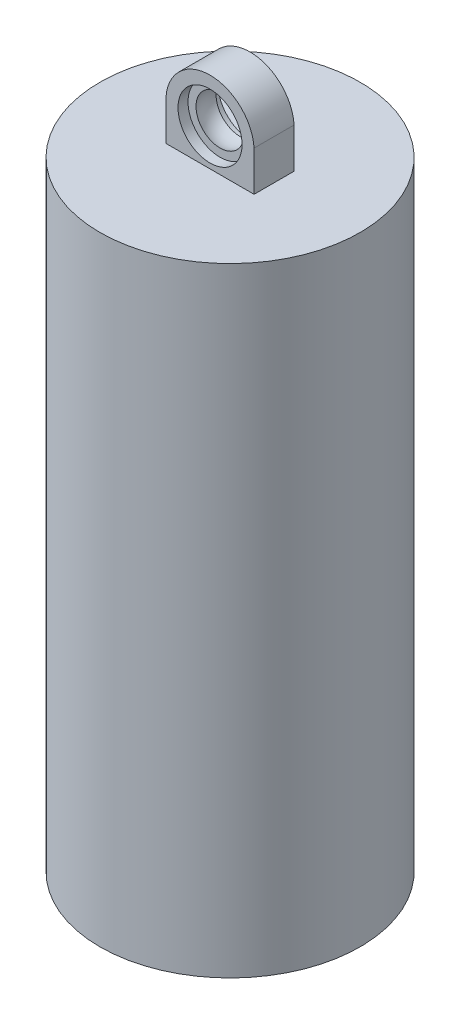
SolidWorks part; units mm, degrees
ref_plane "前视基准面" through (0, 0, 0) normal (0, 0, 1) x (1, 0, 0)
ref_plane "上视基准面" through (0, 0, 0) normal (0, 1, 0) x (1, 0, 0)
ref_plane "右视基准面" through (0, 0, 0) normal (1, 0, 0) x (0, 0, -1)
sketch "草图1" plane through (0, 0, 0) normal (0, 1, 0) x (1, 0, 0)
  circle A0 centre (0, 0) radius 32.5
  dimension "D1" = 65
extrude "凸台-拉伸1" add sketch "草图1" along normal blind 154.5
sketch "草图2" plane through (0, 0, 0) normal (0, -1, 0) x (1, 0, 0)
  circle A0 centre (0, 0) radius 12.5
  dimension "D1" = 25
extrude "凸台-拉伸2" add sketch "草图2" along normal blind 6
sketch "草图3" plane through (0, -6, 0) normal (0, -1, 0) x (1, 0, 0)
  circle A0 centre (0, 0) radius 6
  dimension "D1" = 12
extrude "切除-拉伸1" cut sketch "草图3" against normal blind 80
sketch "草图4" plane through (0, 0, 0) normal (0, 0, 1) x (1, 0, 0)
  line L0 (32.5, 154.5) -> (-32.5, 154.5) construction
  line L1 (-11, 154.5) -> (11, 154.5)
  line L2 (-11, 154.5) -> (-11, 164.5)
  line L4 (11, 154.5) -> (11, 164.5)
  line L5 (0, 193.283) -> (0, 138.3299) construction
  arc A0 (-11, 164.5) -> (11, 164.5) centre (0, 163.7613) cw
  circle A1 centre (0, 163.7613) radius 8
  dimension "D4" = 16
  dimension "D1" = 22
  dimension "D2" = 11
  dimension "D3" = 10
extrude "凸台-拉伸3" add sketch "草图4" against normal mid plane 10
sketch "草图5" plane through (0, 0, 0) normal (0, 0, 1) x (1, 0, 0)
  circle A0 centre (0, 163.7613) radius 8
extrude "凸台-拉伸4" add sketch "草图5" along normal mid plane 5
ref_plane "基准面4" through (0, 0, 4.5) normal (0, 0, 1) x (1, 0, 0)
sketch "草图7" plane through (0, 0, 2.5) normal (0, 0, 1) x (1, 0, 0)
  circle A0 centre (0, 163.7613) radius 6
  dimension "D1" = 12
sketch "草图8" plane through (0, 0, 4.5) normal (0, 0, 1) x (1, 0, 0)
  circle A0 centre (0, 163.7613) radius 4
  dimension "D1" = 8
loft "放样1" add profiles "草图8", "草图7" connector at (3.9808, 163.3699, 4.5) connector at (5.9113, 162.7335, 2.5)
mirror "镜向1" about plane through (0, 0, 0) normal (0, 0, 1) of "放样1"
sketch "草图9" plane through (0, 0, 4.5) normal (0, 0, 1) x (1, 0, 0)
  circle A0 centre (0, 166.7613) radius 2.5
  dimension "D1" = 5
extrude "切除-拉伸2" cut sketch "草图9" against normal blind 31
sketch "草图10" plane through (0, 0, 4.5) normal (0, 0, 1) x (1, 0, 0)
  circle A0 centre (0, 163.7613) radius 6
  circle A4 centre (0, 163.7613) radius 8 construction
extrude "切除-拉伸3" cut sketch "草图10" against normal blind 17
sketch "草图11" plane through (0, 0, 0) normal (0, 0, 1) x (1, 0, 0)
  line L0 (0, 170.2613) -> (0, 157.2613)
  arc A0 (0, 157.2613) -> (0, 170.2613) centre (0, 163.7613) ccw
  dimension "D1" = 13
revolve "切除-旋转1" cut sketch "草图11" angle 360 about L0
